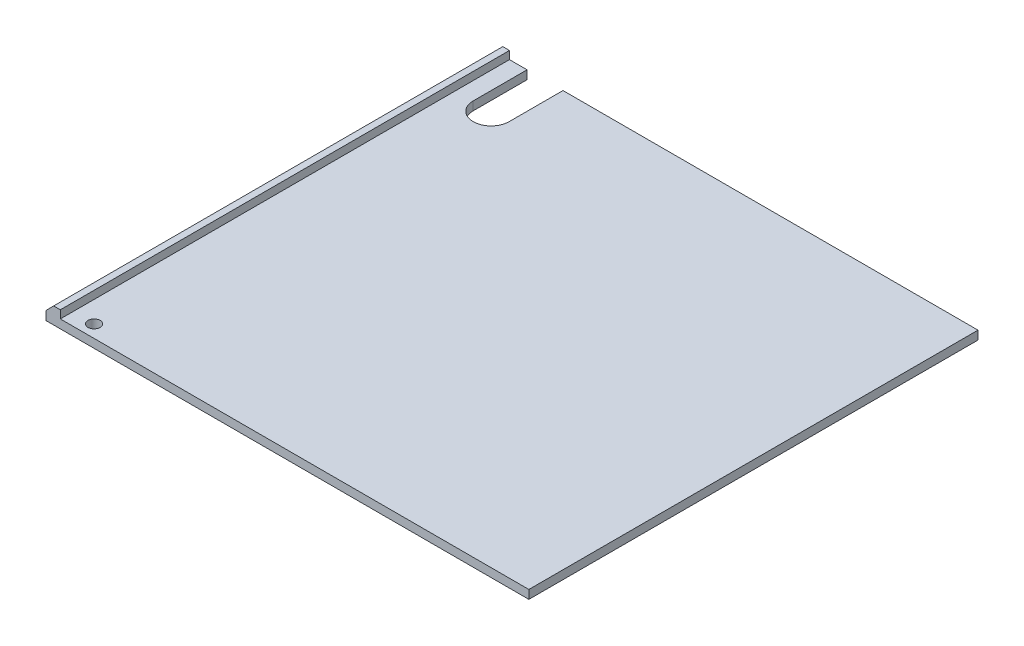
SolidWorks part; units mm, degrees
material "ABS"
ref_plane "Front Plane" through (0, 0, 0) normal (0, 0, 1) x (1, 0, 0)
ref_plane "Top Plane" through (0, 0, 0) normal (0, 1, 0) x (1, 0, 0)
ref_plane "Right Plane" through (0, 0, 0) normal (1, 0, 0) x (0, 0, -1)
ref_axis "Axis1" through (0, 0, 55) along (0, 0, -1)
sketch "Sketch1" plane through (0, 0, 0) normal (0, 1, 0) x (1, 0, 0)
  line L1 (-64.25, 62.5) -> (64.25, 62.5)
  line L2 (-64.25, 62.5) -> (-64.25, -62.5)
  line L3 (-64.25, -62.5) -> (64.25, -62.5)
  line L4 (64.25, 62.5) -> (64.25, -62.5)
  line L5 (-64.25, 62.5) -> (64.25, -62.5) construction
  line L6 (-64.25, -62.5) -> (64.25, 62.5) construction
  point P0 (0, 0)
  dimension "D1" = 128.5
  dimension "D2" = 125
extrude "Boss-Extrude1" add sketch "Sketch1" along normal blind 2.4
sketch "4040-extrusion" plane through (0, 0, 62.5) normal (0, 0, 1) x (1, 0, 0)
  line L0 (-64.25, 0) -> (-64.25, 9.5) construction
  line L1 (-64.25, 9.5) -> (-64.25, 4.3) construction
  line L2 (-64.25, 4.3) -> (-66.05, 2.5) construction
  line L3 (-66.05, 2.5) -> (-66.05, 4.71) construction
  line L4 (-66.05, 4.71) -> (-68.05, 4.71) construction
  line L5 (-68.05, 4.71) -> (-70.2381, 2.5) construction
  line L6 (-70.2381, 2.5) -> (-70.2381, 0) construction
  dimension "D1" = 9.5
  dimension "D2" = 5.2
  dimension "D3" = 7
  dimension "D4" = 1.8
  dimension "D5" = 2.21
  dimension "D6" = 2
  dimension "D7" = 3.11
sketch "Sketch3" plane through (0, 0, 62.5) normal (0, 0, 1) x (1, 0, 0)
  line L0 (-64.25, 2.4) -> (-66.05, 2.4)
  line L1 (-66.05, 2.4) -> (-66.05, 4.71) construction
  line L2 (-66.05, 4.71) -> (-68.05, 4.71) construction
  line L3 (-68.05, 4.71) -> (-70.2381, 2.5) construction
  line L4 (-70.2381, 2.5) -> (-70.2381, 0) construction
  line L5 (-70.2381, 0) -> (-70.1381, 0) construction
  line L6 (-64.25, 0) -> (-64.25, 2.4)
  line L7 (-66.15, 2.4) -> (-66.15, 4.61)
  line L8 (-66.15, 4.61) -> (-68.0083, 4.61)
  line L9 (-68.0083, 4.61) -> (-70.1381, 2.4589)
  line L10 (-70.1381, 2.4589) -> (-70.1381, 0)
  line L11 (-66.15, 2.4) -> (-66.05, 2.4)
  line L12 (-70.1381, 0) -> (-64.25, 0)
  dimension "D1" = 0.1
extrude "Boss-Extrude2" add sketch "Sketch3" against normal up to surface (125 mm away) up to face at (0, 1.2, -62.5)
sketch "Sketch5" plane through (0, 2.4, 0) normal (0, 1, 0) x (1, 0, 0)
  line L0 (-56.25, 62.5) -> (-56.25, 47.5) construction
  line L1 (64.25, 62.5) -> (-66.15, 62.5) construction
  line L2 (-51.25, 62.5) -> (-51.25, 47.5)
  line L3 (-61.25, 62.5) -> (-61.25, 47.5)
  line L5 (-61.25, 62.5) -> (-51.25, 62.5)
  line L6 (-66.15, 62.5) -> (-66.15, -62.5) construction
  arc A0 (-51.25, 62.5) -> (-61.25, 62.5) centre (-56.25, 62.5) ccw
  arc A1 (-61.25, 47.5) -> (-51.25, 47.5) centre (-56.25, 47.5) ccw
  point P4 (-56.25, 55)
  line M5 (64.25, 62.5) -> (-66.15, 62.5)
  dimension "D1" = 5
  dimension "D3" = 15
  dimension "D2" = 9.9
extrude "Cut-Extrude2" cut sketch "Sketch5" against normal through all contours L3 A1 L2 L5 M5 region at (-56.25, 2.4, -53.0036)
sketch "Sketch6" plane through (0, 2.4, 0) normal (0, 1, 0) x (1, 0, 0)
  line L0 (-60.25, -59) -> (-66.15, -59) construction
  line L1 (-66.15, -62.5) -> (64.25, -62.5) construction
  line L3 (-63.75, -62.5) -> (-56.75, -62.5) construction
  line L4 (-63.75, -62.5) -> (-63.75, -55.5) construction
  line L5 (-63.75, -55.5) -> (-56.75, -55.5) construction
  line L6 (-56.75, -62.5) -> (-56.75, -55.5) construction
  line L7 (-63.75, -62.5) -> (-56.75, -55.5) construction
  line L8 (-63.75, -55.5) -> (-56.75, -62.5) construction
  line L9 (-66.15, 62.5) -> (-66.15, -62.5) construction
  circle A0 centre (-60.25, -59) radius 1.7
  point P8 (-60.25, -59)
  dimension "D3" = 3.4
  dimension "D1" = 5.9
  dimension "D2" = 7
extrude "Cut-Extrude3" cut sketch "Sketch6" against normal through all
equation "\"D1@Sketch1\"=125mm+3.5mm"
equation "\"D2@Sketch5\"=5+2+2.3+.1+.5"
